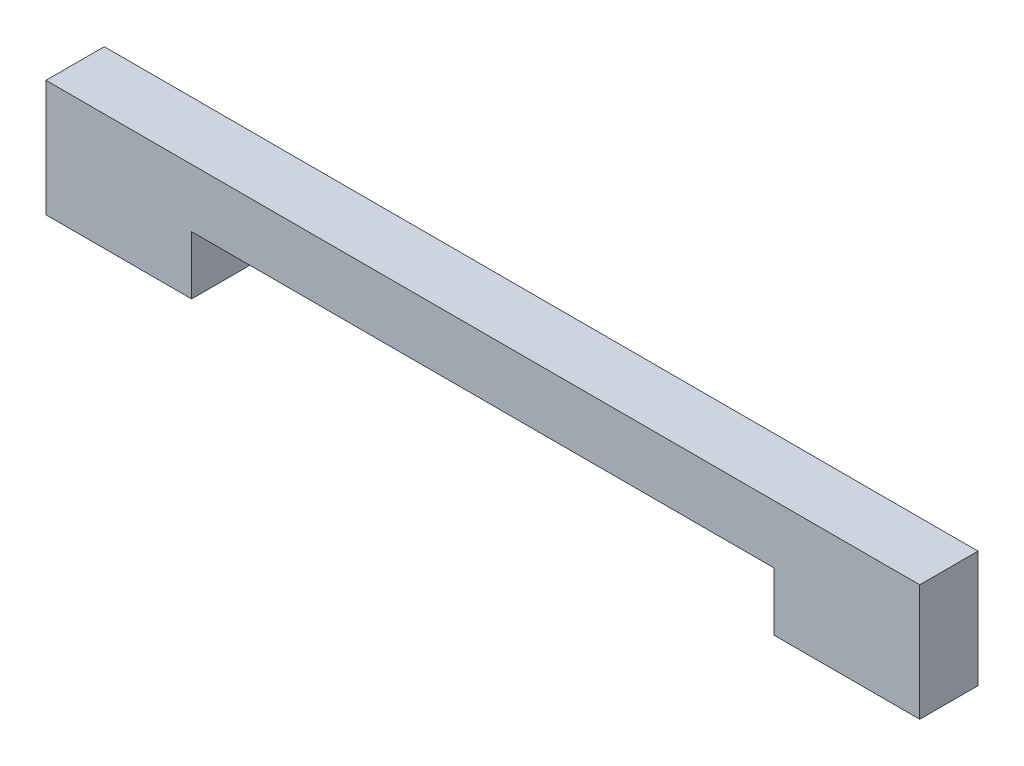
SolidWorks part; units mm, degrees
ref_plane "Front Plane" through (0, 0, 0) normal (0, 0, 1) x (1, 0, 0)
ref_plane "Top Plane" through (0, 0, 0) normal (0, 1, 0) x (1, 0, 0)
ref_plane "Right Plane" through (0, 0, 0) normal (1, 0, 0) x (0, 0, -1)
sketch "Sketch1" plane through (0, 0, 0) normal (0, 0, 1) x (1, 0, 0)
  line L1 (10, 15.1608) -> (50, 15.1608)
  line L2 (0, 0) -> (0, 19.1608)
  line L3 (0, 19.1608) -> (60, 19.1608)
  line L4 (60, 15.1608) -> (60, 19.1608)
  line L6 (0, 0) -> (0, 11.1608)
  line L7 (0, 11.1608) -> (10, 11.1608)
  line L8 (10, 15.1608) -> (10, 11.1608)
  line L10 (60, 15.1608) -> (60, 11.1608)
  line L11 (60, 11.1608) -> (50, 11.1608)
  line L12 (50, 15.1608) -> (50, 11.1608)
  dimension "D1" = 60
  dimension "D2" = 10
  dimension "D3" = 10
  dimension "D4" = 4
  dimension "D5" = 4
extrude "Boss-Extrude1" add sketch "Sketch1" along normal blind 4 contours L1 L12 L11 L10 L4 L3 L2 L7 L8 region at (30, 16.1608, 0)
